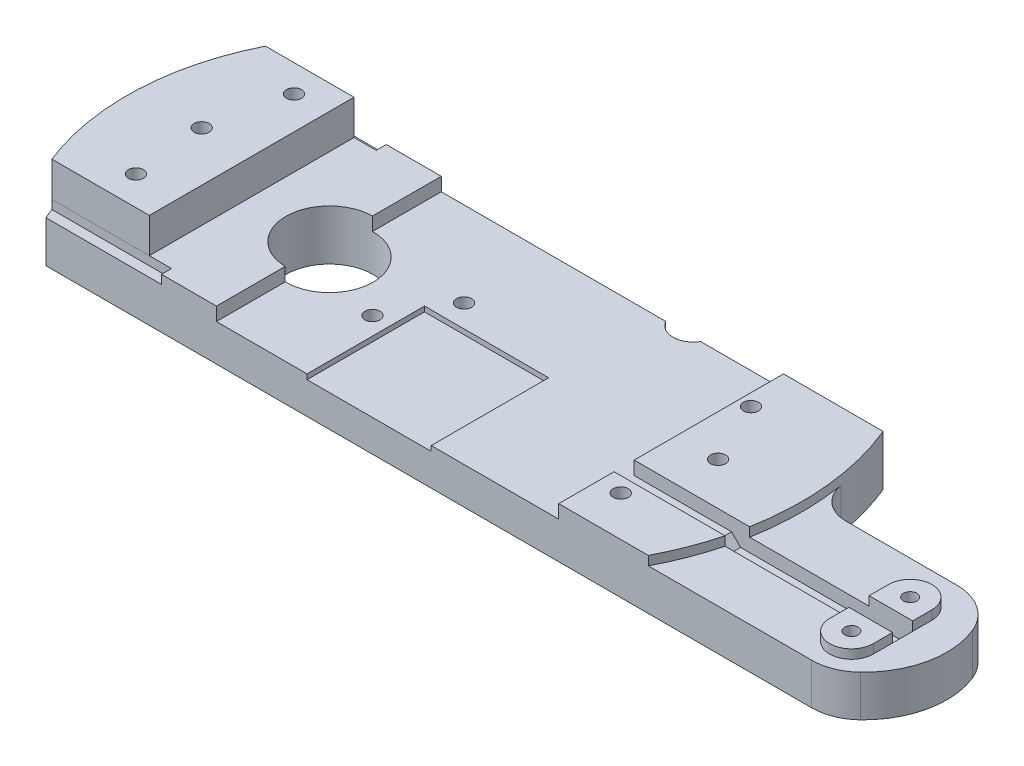
SolidWorks part; units mm, degrees
material "Custom Plastic"
ref_plane "Front Plane" through (0, 0, 0) normal (0, 0, 1) x (1, 0, 0)
ref_plane "Top Plane" through (0, 0, 0) normal (0, 1, 0) x (1, 0, 0)
ref_plane "Right Plane" through (0, 0, 0) normal (1, 0, 0) x (0, 0, -1)
sketch "Sketch1" plane through (0, 0, 0) normal (0, 1, 0) x (1, 0, 0)
  line L1 (-97.5, -33.5) -> (97.5, -33.5)
  line L2 (-97.5, -33.5) -> (-97.5, 33.5)
  line L3 (-97.5, 33.5) -> (97.5, 33.5)
  line L4 (97.5, -33.5) -> (97.5, 33.5)
  line L5 (-97.5, -33.5) -> (97.5, 33.5) construction
  line L6 (-97.5, 33.5) -> (97.5, -33.5) construction
  point P0 (0, 0)
  dimension "D1" = 67
  dimension "D2" = 195
extrude "Boss-Extrude1" add sketch "Sketch1" along normal blind 25.4
sketch "Sketch2" plane through (0, 0, 0) normal (0, -1, 0) x (1, 0, 0)
  line L0 (-97.5, -33.5) -> (-97.5, 33.5) construction
  line L1 (97.5, 33.5) -> (97.5, -33.5) construction
  line L2 (97.5, 33.5) -> (88.5, 33.5)
  line L3 (-97.5, 33.5) -> (97.5, 33.5) construction
  line L4 (97.5, -33.5) -> (91.5, -33.5)
  line L5 (97.5, -33.5) -> (-97.5, -33.5) construction
  line L6 (-97.5, 33.5) -> (-91, 33.5)
  line L7 (-97.5, -33.5) -> (-88, -33.5)
  circle A0 centre (18.0922, -3.2198) radius 79.4078
  circle A1 centre (-22.6589, 2.9929) radius 74.8411
  line M7 (97.5, -33.5) -> (97.5, 33.5)
  line M8 (97.5, 33.5) -> (-97.5, 33.5)
  line M9 (-97.5, 33.5) -> (-97.5, -33.5)
  line M10 (-97.5, -33.5) -> (97.5, -33.5)
  dimension "D1" = 9
  dimension "D2" = 6
  dimension "D3" = 6.5
  dimension "D4" = 9.5
extrude "Cut-Extrude1" cut sketch "Sketch2" against normal through all contours A0 M7 M8 | A0 M10 M7 | A1 M9 M10 | A1 M8 M9 region at (94.8284, 0, 24.4273) region at (95.7123, 0, -25.9883) region at (-95.5654, 0, 25.941) region at (-94.6839, 0, -24.4966)
sketch "Sketch3" plane through (0, 0, 33.5) normal (0, 0, -1) x (-1, 0, 0)
  line L0 (97.5, 25.4) -> (63.2, 25.4)
  line L2 (63.2, 25.4) -> (63.2, 15)
  line L3 (63.2, 15) -> (40.2, 15)
  line L4 (40.2, 15) -> (40.2, 11)
  line L5 (40.2, 11) -> (-61.8, 11)
  line L6 (-91.5, 25.4) -> (88, 25.4) construction
  line L10 (97.5, 0) -> (97.5, 25.4) construction
  line L11 (-61.8, 11) -> (-61.8, 15)
  line L12 (-61.8, 15) -> (-97.5, 15)
  line L13 (-97.5, 25.4) -> (-97.5, 0) construction
  line L14 (-97.5, 15) -> (-97.5, 25.4)
  line L15 (-97.5, 25.4) -> (63.2, 25.4)
  line M13 (-88.5, 0) -> (-88.5, 25.4)
  line M14 (-88.5, 25.4) -> (91, 25.4)
  dimension "D1" = 10.4
  dimension "D2" = 34.3
  dimension "D3" = 23
  dimension "D4" = 4
  dimension "D5" = 102
extrude "Cut-Extrude2" cut sketch "Sketch3" along normal through all contours L11 L12 L2 L3 L4 L5 M13 M14 | L2 L3 L4 L5 L11 L12 L14 L15 region at (12.2699, 18.7206, 33.5)
sketch "Sketch4" plane through (0, 25.4, 0) normal (0, 1, 0) x (1, 0, 0)
  line L0 (-56.5873, 33.5) -> (-56.5873, 30.5)
  line L1 (-63.2, 33.5) -> (-88, 33.5) construction
  line L2 (-56.5873, 30.5) -> (-89.5873, 30.5)
  line L3 (-56.5873, -33.5) -> (-56.5873, -30.5)
  line L4 (-91, -33.5) -> (-63.2, -33.5) construction
  line L5 (-56.5873, -30.5) -> (-92.2617, -30.5)
  line L6 (-56.5873, 33.5) -> (-63.2, 33.5)
  line L7 (-56.5873, -33.5) -> (-63.2, -33.5)
  arc A0 (-88, 33.5) -> (-91, -33.5) centre (-22.6589, -2.9929) ccw construction
  line M5 (-91, -33.5) -> (-63.2, -33.5)
  line M6 (-63.2, -33.5) -> (-63.2, 33.5)
  line M7 (-63.2, 33.5) -> (-88, 33.5)
  arc M8 (-88, 33.5) -> (-91, -33.5) centre (-22.6589, -2.9929) ccw
  dimension "D1" = 3
  dimension "D2" = 3
  dimension "D3" = 33
extrude "Cut-Extrude3" cut sketch "Sketch4" against normal blind 13 contours L2 M6 M7 M8 | L0 L6 L2 M6 | L5 M6 M8 M5 | L7 L3 L5 M6 region at (-59.8937, 25.4, -32) region at (-76.0082, 25.4, -31.9845) region at (-77.4242, 25.4, 31.9889) region at (-59.8937, 25.4, 32)
sketch "Sketch6" plane through (0, 0, 0) normal (0, -1, 0) x (1, 0, 0)
  line L0 (-63.2, -33.5) -> (-97.5, -33.5)
  line L1 (91.5, -33.5) -> (-88, -33.5) construction
  line L2 (-63.2, -33.5) -> (-63.2, 33.5)
  line L3 (-91, 33.5) -> (88.5, 33.5) construction
  line L4 (-63.2, -9) -> (-28.1, -9) construction
  line L5 (-63.2, 8.7) -> (-18.5, 8.7) construction
  line L6 (-63.2, -8.2) -> (-8.1, -8.2) construction
  line L8 (91.5, -33.5) -> (-88, -33.5) construction
  line L9 (-97.5, -33.5) -> (-97.5, 33.5)
  line L10 (-97.5, 33.5) -> (-63.2, 33.5)
  circle A1 centre (-18.5, 8.7) radius 2.25
  circle A2 centre (74.1, -1.7) radius 2.25
  circle A3 centre (68.3, 21.5) radius 2.25
  circle A4 centre (65.4, -20.2) radius 2.25
  circle A5 centre (-8.1, -8.2) radius 2.25
  circle A6 centre (-75.9, 21.8) radius 2.25
  circle A7 centre (-78, 0.1) radius 2.25
  circle A8 centre (-73, -22.4) radius 2.25
  arc A10 (-91, 33.5) -> (-88, -33.5) centre (-22.6589, 2.9929) ccw construction
  dimension "D22" = 4.5
  dimension "D3" = 35.1
  dimension "D4" = 34.3
  dimension "D5" = 44.7
  dimension "D6" = 24.5
  dimension "D7" = 55.1
  dimension "D8" = 42.2
  dimension "D9" = 137.3
  dimension "D10" = 128.6
  dimension "D11" = 131.5
  dimension "D12" = 9.8
  dimension "D13" = 14.8
  dimension "D14" = 12.7
  dimension "D15" = 11.1
  dimension "D16" = 33.6
  dimension "D17" = 55.3
  dimension "D18" = 31.8
  dimension "D19" = 55
  dimension "D20" = 13.3
  dimension "D21" = 25.3
extrude "Cut-Extrude4" cut sketch "Sketch6" against normal through all contours A5 | A1 | A6 | A7 | A8 | A4 | A2 | A3 region at (-18.5, 0, 8.7) region at (74.1, 0, -1.7) region at (68.3, 0, 21.5) region at (65.4, 0, -20.2) region at (-8.1, 0, -8.2) region at (-75.9, 0, 21.8) region at (-78, 0, 0.1) region at (-73, 0, -22.4)
sketch "Sketch7" plane through (0, 11, 0) normal (0, 1, 0) x (1, 0, 0)
  line L1 (-13.2, 1.5) -> (23.8, 1.5)
  line L2 (-13.2, 1.5) -> (-13.2, -33.5)
  line L3 (-13.2, -33.5) -> (23.8, -33.5)
  line L4 (23.8, 1.5) -> (23.8, -33.5)
  line L8 (-63.2, 30.5) -> (-63.2, -30.5) construction
  line L9 (-63.2, 30.5) -> (-63.2, -30.5) construction
  line L10 (-40.2, -33.5) -> (61.8, -33.5) construction
  dimension "D1" = 50
  dimension "D2" = 87
  dimension "D3" = 35
extrude "Cut-Extrude5" cut sketch "Sketch7" against normal blind 1.5
sketch "Sketch8" plane through (0, 25.4, 0) normal (0, 1, 0) x (1, 0, 0)
  line L0 (-56.5873, -33.5) -> (-97.5, -33.5)
  line L1 (-97.5, -33.5) -> (-97.5, 33.5)
  line L3 (-97.5, 33.5) -> (31.9, 33.5)
  line L6 (31.9, 36.5) -> (31.9, 30.5)
  line L7 (31.9, 33.5) -> (37.0962, 33.5)
  line L10 (-56.5873, 33.5) -> (-88, 33.5) construction
  line L11 (-40.2, 33.5) -> (61.8, 33.5) construction
  circle A1 centre (31.9, 36.5) radius 6
  arc A2 (-89.5873, 30.5) -> (-92.2617, -30.5) centre (-22.6589, -2.9929) ccw construction
  dimension "D1" = 12
  dimension "D2" = 129.4
extrude "Cut-Extrude6" cut sketch "Sketch8" against normal blind 18.5 contours L6 A1 L7 | L3 A1 L6 region at (29.8648, 25.4, -32.2699) region at (33.9352, 25.4, -32.2699)
sketch "Sketch9" plane through (0, 0, 0) normal (0, -1, 0) x (1, 0, 0)
  line L0 (88.5, 33.5) -> (137.2004, 33.5)
  line L1 (139.5727, -7.5) -> (97.3846, -7.5)
  arc A0 (153.4738, 1.8643) -> (147.5429, 29.3643) centre (130.3054, 11.2571) ccw
  arc A1 (91.5, -33.5) -> (88.5, 33.5) centre (18.0922, -3.2198) ccw construction
  arc A2 (142.3827, -10.6321) -> (147.5429, 29.3643) centre (130.3054, 11.2571) ccw construction
  arc A3 (147.5429, 29.3643) -> (137.2004, 33.5) centre (137.2004, 18.5) ccw
  arc A4 (147.5429, 29.3643) -> (137.9704, 33.4802) centre (137.2004, 18.5) ccw construction
  arc A5 (139.5727, -7.5) -> (153.4738, 1.8643) centre (139.5727, 7.5) ccw
  circle A6 centre (112.8181, -27.5) radius 16 construction
  circle A7 centre (103.4238, 59.4942) radius 16 construction
  circle A8 centre (112.8181, -27.5) radius 20 construction
  arc A9 (97.3846, -7.5) -> (88.5, 33.5) centre (18.0922, -3.2198) ccw
  circle A10 centre (138.3, 5.25) radius 2
  circle A11 centre (138.3, 22.75) radius 2
  circle A12 centre (138.3, 22.75) radius 2 construction
  circle A13 centre (138.3, 5.25) radius 2 construction
  dimension "D1" = 4
extrude "Boss-Extrude2" add sketch "Sketch9" against normal offset from surface (12.3 mm away) 1.3 up to face at (-16.25, 11, 8.7) offset beyond the face yes
fillet "Fillet1" radius 10 1 edges at (97.3846, 6.15, -7.5)
sketch "Sketch10" plane through (0, 0, 0) normal (0, -1, 0) x (1, 0, 0)
  circle A0 centre (-40.0178, 0) radius 13
  dimension "D1" = 26
extrude "Cut-Extrude7" cut sketch "Sketch10" against normal through all
sketch "Sketch11" plane through (0, 12.3, 0) normal (0, 1, 0) x (1, 0, 0)
  line L0 (138.3, -5.25) -> (138.3, -22.75) construction
  line L1 (144.8, -5.25) -> (144.8, -22.75)
  line L2 (131.8, -5.25) -> (131.8, -22.75)
  line L3 (131.8, -11) -> (144.8, -11)
  line L4 (131.8, -17) -> (144.8, -17)
  line L5 (131.8, -14) -> (144.8, -14) construction
  arc A0 (144.8, -5.25) -> (131.8, -5.25) centre (138.3, -5.25) ccw
  arc A1 (131.8, -22.75) -> (144.8, -22.75) centre (138.3, -22.75) ccw
  point P4 (138.3, -14)
  circle M15 centre (138.3, -22.75) radius 2
  circle M16 centre (138.3, -5.25) radius 2
  dimension "D1" = 13
  dimension "D2" = 6
extrude "Boss-Extrude3" add sketch "Sketch11" along normal up to surface (2.7 mm away) contours L1 A0 L2 L3 M16 | L2 A1 L1 L4 M15 region at (144.6214, 12.3, 8.125) region at (144.6214, 12.3, 19.875) up to face at (70.55, 15, 21.5)
sketch "Sketch12" plane through (0, 0, 11) normal (0, 0, 1) x (1, 0, 0)
  line L0 (144.8, 15) -> (144.8, 8.3)
  line L1 (144.8, 8.3) -> (93.5, 8.3)
  line L3 (97.5, 12.3) -> (88.5, 12.3) construction
  line L4 (90.8, 11) -> (61.8, 11)
  line L5 (61.8, 11) -> (61.8, 15)
  line L6 (61.8, 15) -> (88.5, 15) construction
  line L7 (61.8, 15) -> (144.8, 15)
  line L10 (97.5, 12.3) -> (93.5, 12.3) construction
  line L12 (88.5, 12.3) -> (137.2004, 12.3) construction
  line L13 (93.5, 12.3) -> (93.5, 8.3) construction
  line L14 (61.8, 11) -> (61.8, 15) construction
  line L15 (23.8, 11) -> (61.8, 11) construction
  line L16 (93.5, 8.3) -> (90.8, 11)
  dimension "D1" = 45
extrude "Cut-Extrude8" cut sketch "Sketch12" along normal up to surface (6 mm away) up to face at (138.3, 13.65, 17)
split "Split1" bodies to split 116 resulting bodies 114 115 split by face at (-52.6367, 15, 0)
